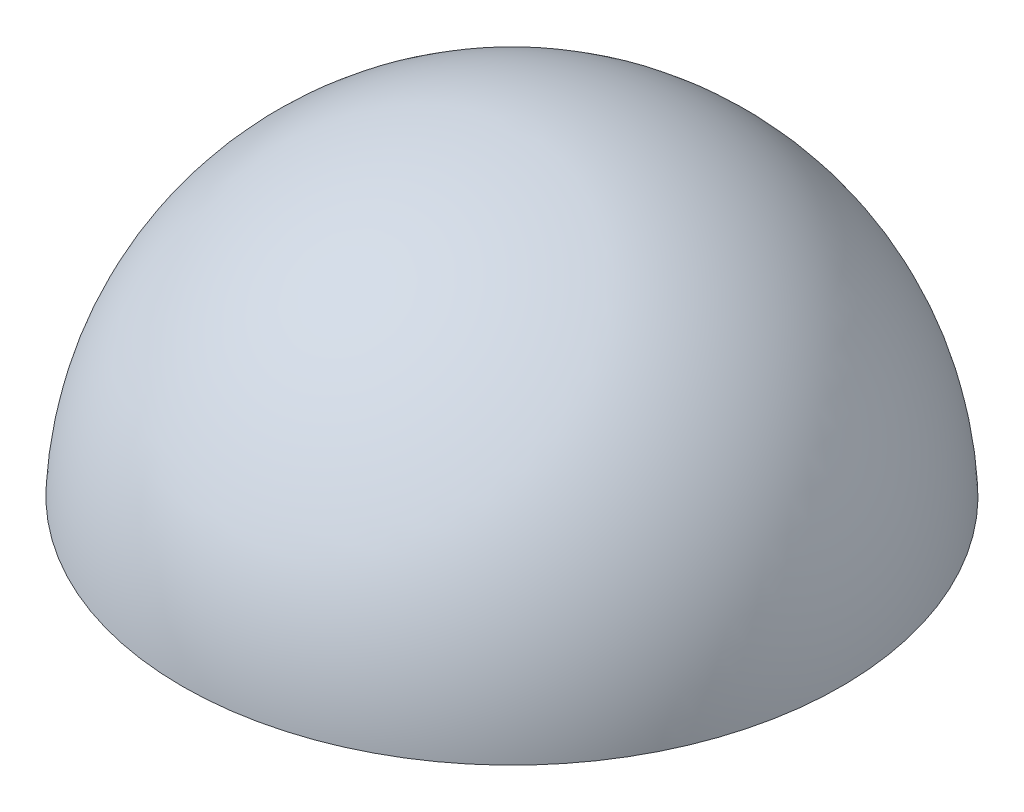
SolidWorks part; units mm, degrees
ref_plane "Front Plane" through (0, 0, 0) normal (0, 0, 1) x (1, 0, 0)
ref_plane "Top Plane" through (0, 0, 0) normal (0, 1, 0) x (1, 0, 0)
ref_plane "Right Plane" through (0, 0, 0) normal (1, 0, 0) x (0, 0, -1)
sketch "Sketch1" plane through (0, 0, 0) normal (0, 1, 0) x (1, 0, 0)
  line L0 (0, -44.45) -> (0, 44.45)
  arc A0 (0, 44.45) -> (0, -44.45) centre (0, 0) ccw
  arc A1 (0, 42.45) -> (0, -42.45) centre (0, 0) ccw
  circle A3 centre (0, 0) radius 44.45 construction
  circle A4 centre (0, 0) radius 42.45 construction
  point P1 (42.45, 0)
  point P6 (42.5077, 12.9959)
  dimension "D1" = 88.9
  dimension "D2" = 2
revolve "Revolve1" add sketch "Sketch1" angle 180 about L0 region at (-43.4561, 0, 0)
sketch "Sketch2" plane through (0, 0, 0) normal (0, 1, 0) x (1, 0, 0)
  circle A0 centre (0, 0) radius 44.45
extrude "Cut-Extrude1" cut sketch "Sketch2" along normal blind 2
sketch "30deg" plane through (0, 0, 0) normal (1, 0, 0) x (0, 0, -1)
  line L0 (0, 0) -> (38.4948, 22.225) construction
  line L1 (0, 0) -> (44.45, 0) construction
  line L7 (0, 0) -> (22.225, 38.4948) construction
  line L8 (0, 0) -> (44.45, 0) construction
  line L10 (0, 0) -> (38.4948, 22.225) construction
  line L25 (0, 0) -> (0, 49000) construction
  dimension "D2" = 3
  dimension "D3" = 30
  dimension "D1" = 44.45
sketch "Sketch4" plane through (0, 0, 0) normal (0, 1, 0) x (1, 0, 0)
  line L0 (0, 0) -> (0, 43.45)
  line L1 (0.5, 44.45) -> (-0.5, 44.45)
  line L2 (-0.5, 43.45) -> (0.5, 43.45)
  line L3 (-0.5, 43.45) -> (-0.5, 44.45)
  line L4 (0.5, 43.45) -> (0.5, 44.45)
  line L5 (0, 0) -> (21.725, 37.6288)
  line L6 (21.292, 37.8788) -> (21.792, 38.7448)
  line L7 (21.292, 37.8788) -> (22.158, 37.3788)
  line L8 (22.158, 37.3788) -> (22.658, 38.2448)
  line L9 (22.658, 38.2448) -> (21.792, 38.7448)
  line L10 (0, 0) -> (37.6288, 21.725)
  line L11 (37.3788, 22.158) -> (38.2448, 22.658)
  line L12 (37.3788, 22.158) -> (37.8788, 21.292)
  line L13 (37.8788, 21.292) -> (38.7448, 21.792)
  line L14 (38.7448, 21.792) -> (38.2448, 22.658)
  line L15 (0, 0) -> (43.45, 0)
  line L16 (43.45, 0.5) -> (44.45, 0.5)
  line L17 (43.45, 0.5) -> (43.45, -0.5)
  line L18 (43.45, -0.5) -> (44.45, -0.5)
  line L19 (44.45, -0.5) -> (44.45, 0.5)
  line L20 (0, 0) -> (37.6288, -21.725)
  line L21 (37.8788, -21.292) -> (38.7448, -21.792)
  line L22 (37.8788, -21.292) -> (37.3788, -22.158)
  line L23 (37.3788, -22.158) -> (38.2448, -22.658)
  line L24 (38.2448, -22.658) -> (38.7448, -21.792)
  line L25 (0, 0) -> (21.725, -37.6288)
  line L26 (22.158, -37.3788) -> (22.658, -38.2448)
  line L27 (22.158, -37.3788) -> (21.292, -37.8788)
  line L28 (21.292, -37.8788) -> (21.792, -38.7448)
  line L29 (21.792, -38.7448) -> (22.658, -38.2448)
  line L30 (0, 0) -> (0, -43.45)
  line L31 (0.5, -43.45) -> (0.5, -44.45)
  line L32 (0.5, -43.45) -> (-0.5, -43.45)
  line L33 (-0.5, -43.45) -> (-0.5, -44.45)
  line L34 (-0.5, -44.45) -> (0.5, -44.45)
  line L35 (0, 0) -> (-21.725, -37.6288)
  line L36 (-21.292, -37.8788) -> (-21.792, -38.7448)
  line L37 (-21.292, -37.8788) -> (-22.158, -37.3788)
  line L38 (-22.158, -37.3788) -> (-22.658, -38.2448)
  line L39 (-22.658, -38.2448) -> (-21.792, -38.7448)
  line L40 (0, 0) -> (-37.6288, -21.725)
  line L41 (-37.3788, -22.158) -> (-38.2448, -22.658)
  line L42 (-37.3788, -22.158) -> (-37.8788, -21.292)
  line L43 (-37.8788, -21.292) -> (-38.7448, -21.792)
  line L44 (-38.7448, -21.792) -> (-38.2448, -22.658)
  line L45 (0, 0) -> (-43.45, 0)
  line L46 (-43.45, -0.5) -> (-44.45, -0.5)
  line L47 (-43.45, -0.5) -> (-43.45, 0.5)
  line L48 (-43.45, 0.5) -> (-44.45, 0.5)
  line L49 (-44.45, 0.5) -> (-44.45, -0.5)
  line L50 (0, 0) -> (-37.6288, 21.725)
  line L51 (-37.8788, 21.292) -> (-38.7448, 21.792)
  line L52 (-37.8788, 21.292) -> (-37.3788, 22.158)
  line L53 (-37.3788, 22.158) -> (-38.2448, 22.658)
  line L54 (-38.2448, 22.658) -> (-38.7448, 21.792)
  line L55 (0, 0) -> (-21.725, 37.6288)
  line L56 (-22.158, 37.3788) -> (-22.658, 38.2448)
  line L57 (-22.158, 37.3788) -> (-21.292, 37.8788)
  line L58 (-21.292, 37.8788) -> (-21.792, 38.7448)
  line L59 (-21.792, 38.7448) -> (-22.658, 38.2448)
  line L60 (0, 0) -> (0, 43.45) construction
  line L61 (0, 0) -> (21.725, 37.6288) construction
  circle A0 centre (0, 0) radius 44.45 construction
  point P7 (0, 44.45)
  point P10 (0, 43.45)
  dimension "D1" = 88.9
  dimension "D2" = 1
  dimension "D3" = 1
  dimension "D5" = 30
  dimension "D4" = 12
ref_plane "Plane1" through (0, 44.45, 0) normal (0, 1, 0) x (1, 0, 0)
sketch "Sketch5" plane through (0, 44.45, 0) normal (0, 1, 0) x (1, 0, 0)
  circle A0 centre (0, 0) radius 0.5
  dimension "D1" = 1
sketch "Sketch6" plane through (0, 0, 0) normal (0, 0, 1) x (1, 0, 0)
  line L0 (44.45, 0) -> (-44.45, 0) construction
  line L1 (-43.45, 0) -> (-44.45, 0) construction
  arc A0 (-44.45, 0) -> (0, 44.45) centre (0, 0) cw
ref_axis "Axis1" through (0, 117.8347, 0) along (0, -1, 0)
sketch "Sketch7" plane through (0, 44.45, 0) normal (0, 1, 0) x (1, 0, 0)
  line L0 (0, 0) -> (0, 88.8986) construction
  line L4 (-0.5, 38.9916) -> (-0.5, 88.8986)
  line L5 (0.5, 38.9916) -> (0.5, 88.8986)
  line L7 (-0.5, 22.7195) -> (-0.5, 37.9915)
  line L9 (0.5, 22.7195) -> (0.5, 37.9915)
  line L10 (0, 0) -> (44.4493, 76.9884) construction
  line L11 (19.0628, 34.0177) -> (44.0163, 77.2384)
  line L12 (19.9288, 33.5177) -> (44.8823, 76.7384)
  line L13 (10.9267, 19.9257) -> (18.5628, 33.1516)
  line L14 (11.7928, 19.4257) -> (19.4288, 32.6516)
  line L17 (0, 0) -> (76.9884, 44.4493) construction
  line L18 (33.5177, 19.9288) -> (76.7384, 44.8823)
  line L19 (34.0177, 19.0628) -> (77.2384, 44.0163)
  line L20 (19.4257, 11.7928) -> (32.6516, 19.4288)
  line L21 (19.9257, 10.9267) -> (33.1516, 18.5628)
  line L24 (0, 0) -> (88.8986, 0) construction
  line L25 (38.9916, 0.5) -> (88.8986, 0.5)
  line L26 (38.9916, -0.5) -> (88.8986, -0.5)
  line L27 (22.7195, 0.5) -> (37.9915, 0.5)
  line L28 (22.7195, -0.5) -> (37.9915, -0.5)
  line L31 (0, 0) -> (76.9884, -44.4493) construction
  line L32 (34.0177, -19.0628) -> (77.2384, -44.0163)
  line L33 (33.5177, -19.9288) -> (76.7384, -44.8823)
  line L34 (19.9257, -10.9267) -> (33.1516, -18.5628)
  line L35 (19.4257, -11.7928) -> (32.6516, -19.4288)
  line L38 (0, 0) -> (44.4493, -76.9884) construction
  line L39 (19.9288, -33.5177) -> (44.8823, -76.7384)
  line L40 (19.0628, -34.0177) -> (44.0163, -77.2384)
  line L41 (11.7928, -19.4257) -> (19.4288, -32.6516)
  line L42 (10.9267, -19.9257) -> (18.5628, -33.1516)
  line L45 (0, 0) -> (0, -88.8986) construction
  line L46 (0.5, -38.9916) -> (0.5, -88.8986)
  line L47 (-0.5, -38.9916) -> (-0.5, -88.8986)
  line L48 (0.5, -22.7195) -> (0.5, -37.9915)
  line L49 (-0.5, -22.7195) -> (-0.5, -37.9915)
  line L52 (0, 0) -> (-44.4493, -76.9884) construction
  line L53 (-19.0628, -34.0177) -> (-44.0163, -77.2384)
  line L54 (-19.9288, -33.5177) -> (-44.8823, -76.7384)
  line L55 (-10.9267, -19.9257) -> (-18.5628, -33.1516)
  line L56 (-11.7928, -19.4257) -> (-19.4288, -32.6516)
  line L59 (0, 0) -> (-76.9884, -44.4493) construction
  line L60 (-33.5177, -19.9288) -> (-76.7384, -44.8823)
  line L61 (-34.0177, -19.0628) -> (-77.2384, -44.0163)
  line L62 (-19.4257, -11.7928) -> (-32.6516, -19.4288)
  line L63 (-19.9257, -10.9267) -> (-33.1516, -18.5628)
  line L66 (0, 0) -> (-88.8986, 0) construction
  line L67 (-38.9916, -0.5) -> (-88.8986, -0.5)
  line L68 (-38.9916, 0.5) -> (-88.8986, 0.5)
  line L69 (-22.7195, -0.5) -> (-37.9915, -0.5)
  line L70 (-22.7195, 0.5) -> (-37.9915, 0.5)
  line L73 (0, 0) -> (-76.9884, 44.4493) construction
  line L74 (-34.0177, 19.0628) -> (-77.2384, 44.0163)
  line L75 (-33.5177, 19.9288) -> (-76.7384, 44.8823)
  line L76 (-19.9257, 10.9267) -> (-33.1516, 18.5628)
  line L77 (-19.4257, 11.7928) -> (-32.6516, 19.4288)
  line L80 (0, 0) -> (-44.4493, 76.9884) construction
  line L81 (-19.9288, 33.5177) -> (-44.8823, 76.7384)
  line L82 (-19.0628, 34.0177) -> (-44.0163, 77.2384)
  line L83 (-11.7928, 19.4257) -> (-19.4288, 32.6516)
  line L84 (-10.9267, 19.9257) -> (-18.5628, 33.1516)
  line L87 (0, 0) -> (0.5, 0) construction
  line L89 (-0.5, 1.866) -> (-0.5, 21.7192)
  line L90 (-0.5, 1.866) -> (-10.4266, 19.0594)
  line L91 (0.5, 1.866) -> (10.4266, 19.0594)
  line L92 (0.5, 1.866) -> (0.5, 21.7192)
  line L93 (1.366, 1.366) -> (18.5594, 11.2926)
  line L94 (1.366, 1.366) -> (11.2926, 18.5594)
  line L95 (1.866, 0.5) -> (21.7192, 0.5)
  line L96 (1.866, 0.5) -> (19.0594, 10.4266)
  line L97 (1.866, -0.5) -> (19.0594, -10.4266)
  line L98 (1.866, -0.5) -> (21.7192, -0.5)
  line L99 (1.366, -1.366) -> (11.2926, -18.5594)
  line L100 (1.366, -1.366) -> (18.5594, -11.2926)
  line L101 (0.5, -1.866) -> (0.5, -21.7192)
  line L102 (0.5, -1.866) -> (10.4266, -19.0594)
  line L103 (-0.5, -1.866) -> (-10.4266, -19.0594)
  line L104 (-0.5, -1.866) -> (-0.5, -21.7192)
  line L105 (-1.366, -1.366) -> (-11.2926, -18.5594)
  line L106 (-1.366, -1.366) -> (-18.5594, -11.2926)
  line L107 (-1.866, -0.5) -> (-21.7192, -0.5)
  line L108 (-1.866, -0.5) -> (-19.0594, -10.4266)
  line L109 (-1.866, 0.5) -> (-19.0594, 10.4266)
  line L110 (-1.866, 0.5) -> (-21.7192, 0.5)
  line L111 (-1.366, 1.366) -> (-11.2926, 18.5594)
  line L112 (-1.366, 1.366) -> (-18.5594, 11.2926)
  circle A0 centre (0, 0) radius 22.225 construction
  circle A1 centre (0, 0) radius 38.4948 construction
  arc A2 (-0.5, 38.9916) -> (-19.0628, 34.0177) centre (0, 0) ccw
  arc A3 (-0.5, 22.7195) -> (-10.9267, 19.9257) centre (0, 0) ccw
  arc A4 (-0.5, 37.9915) -> (-18.5628, 33.1516) centre (0, 0) ccw
  arc A5 (-0.5, 21.7192) -> (-10.4266, 19.0594) centre (0, 0) ccw
  arc A6 (0.5, 88.8986) -> (-0.5, 88.8986) centre (0, 0) ccw
  circle A9 centre (0, 0) radius 88.9 construction
  circle A10 centre (0, 0) radius 38.9948 construction
  circle A11 centre (0, 0) radius 37.9948 construction
  circle A13 centre (0, 0) radius 21.725 construction
  circle A14 centre (0, 0) radius 22.725 construction
  arc A15 (44.8823, 76.7384) -> (44.0163, 77.2384) centre (0, 0) ccw
  arc A16 (77.2384, 44.0163) -> (76.7384, 44.8823) centre (0, 0) ccw
  arc A17 (88.8986, -0.5) -> (88.8986, 0.5) centre (0, 0) ccw
  arc A18 (76.7384, -44.8823) -> (77.2384, -44.0163) centre (0, 0) ccw
  arc A19 (44.0163, -77.2384) -> (44.8823, -76.7384) centre (0, 0) ccw
  arc A20 (-0.5, -88.8986) -> (0.5, -88.8986) centre (0, 0) ccw
  arc A21 (-44.8823, -76.7384) -> (-44.0163, -77.2384) centre (0, 0) ccw
  arc A22 (-77.2384, -44.0163) -> (-76.7384, -44.8823) centre (0, 0) ccw
  arc A23 (-88.8986, 0.5) -> (-88.8986, -0.5) centre (0, 0) ccw
  arc A24 (-76.7384, 44.8823) -> (-77.2384, 44.0163) centre (0, 0) ccw
  arc A25 (-44.0163, 77.2384) -> (-44.8823, 76.7384) centre (0, 0) ccw
  arc A26 (-34.0177, 19.0628) -> (-38.9916, 0.5) centre (0, 0) ccw
  arc A27 (-33.1516, 18.5628) -> (-37.9915, 0.5) centre (0, 0) ccw
  arc A28 (-19.9288, 33.5177) -> (-33.5177, 19.9288) centre (0, 0) ccw
  arc A29 (-19.4288, 32.6516) -> (-32.6516, 19.4288) centre (0, 0) ccw
  arc A30 (19.0628, 34.0177) -> (0.5, 38.9916) centre (0, 0) ccw
  arc A31 (18.5628, 33.1516) -> (0.5, 37.9915) centre (0, 0) ccw
  arc A32 (32.6516, 19.4288) -> (19.4288, 32.6516) centre (0, 0) ccw
  arc A33 (33.5177, 19.9288) -> (19.9288, 33.5177) centre (0, 0) ccw
  arc A34 (37.9915, 0.5) -> (33.1516, 18.5628) centre (0, 0) ccw
  arc A35 (38.9916, 0.5) -> (34.0177, 19.0628) centre (0, 0) ccw
  arc A36 (33.1516, -18.5628) -> (37.9915, -0.5) centre (0, 0) ccw
  arc A37 (34.0177, -19.0628) -> (38.9916, -0.5) centre (0, 0) ccw
  arc A38 (19.4288, -32.6516) -> (32.6516, -19.4288) centre (0, 0) ccw
  arc A39 (19.9288, -33.5177) -> (33.5177, -19.9288) centre (0, 0) ccw
  arc A40 (0.5, -37.9915) -> (18.5628, -33.1516) centre (0, 0) ccw
  arc A41 (0.5, -38.9916) -> (19.0628, -34.0177) centre (0, 0) ccw
  arc A42 (-18.5628, -33.1516) -> (-0.5, -37.9915) centre (0, 0) ccw
  arc A43 (-19.0628, -34.0177) -> (-0.5, -38.9916) centre (0, 0) ccw
  arc A44 (-33.5177, -19.9288) -> (-19.9288, -33.5177) centre (0, 0) ccw
  arc A45 (-32.6516, -19.4288) -> (-19.4288, -32.6516) centre (0, 0) ccw
  arc A46 (-38.9916, -0.5) -> (-34.0177, -19.0628) centre (0, 0) ccw
  arc A47 (-37.9915, -0.5) -> (-33.1516, -18.5628) centre (0, 0) ccw
  arc A48 (-11.7928, 19.4257) -> (-19.4257, 11.7928) centre (0, 0) ccw
  arc A49 (-11.2926, 18.5594) -> (-18.5594, 11.2926) centre (0, 0) ccw
  arc A50 (-19.9257, 10.9267) -> (-22.7195, 0.5) centre (0, 0) ccw
  arc A51 (-19.0594, 10.4266) -> (-21.7192, 0.5) centre (0, 0) ccw
  arc A52 (-21.7192, -0.5) -> (-19.0594, -10.4266) centre (0, 0) ccw
  arc A53 (-22.7195, -0.5) -> (-19.9257, -10.9267) centre (0, 0) ccw
  arc A54 (10.4266, 19.0594) -> (0.5, 21.7192) centre (0, 0) ccw
  arc A55 (10.9267, 19.9257) -> (0.5, 22.7195) centre (0, 0) ccw
  arc A56 (18.5594, 11.2926) -> (11.2926, 18.5594) centre (0, 0) ccw
  arc A57 (19.4257, 11.7928) -> (11.7928, 19.4257) centre (0, 0) ccw
  arc A58 (21.7192, 0.5) -> (19.0594, 10.4266) centre (0, 0) ccw
  arc A59 (22.7195, 0.5) -> (19.9257, 10.9267) centre (0, 0) ccw
  arc A60 (19.9257, -10.9267) -> (22.7195, -0.5) centre (0, 0) ccw
  arc A61 (19.0594, -10.4266) -> (21.7192, -0.5) centre (0, 0) ccw
  arc A62 (11.2926, -18.5594) -> (18.5594, -11.2926) centre (0, 0) ccw
  arc A63 (11.7928, -19.4257) -> (19.4257, -11.7928) centre (0, 0) ccw
  arc A64 (0.5, -22.7195) -> (10.9267, -19.9257) centre (0, 0) ccw
  arc A65 (0.5, -21.7192) -> (10.4266, -19.0594) centre (0, 0) ccw
  arc A66 (-10.4266, -19.0594) -> (-0.5, -21.7192) centre (0, 0) ccw
  arc A67 (-10.9267, -19.9257) -> (-0.5, -22.7195) centre (0, 0) ccw
  arc A68 (-19.4257, -11.7928) -> (-11.7928, -19.4257) centre (0, 0) ccw
  arc A69 (-18.5594, -11.2926) -> (-11.2926, -18.5594) centre (0, 0) ccw
  point P11 (21.725, 0)
  point P13 (22.725, 0)
  point P17 (0.5, 0)
  point P19 (-0.5, 0)
  point P27 (38.9948, 0)
  point P30 (37.9948, 0)
  point P114 (-1.366, 1.366)
  dimension "D5" = 177.8
  dimension "D1" = 0.5
  dimension "D2" = 0.5
  dimension "D6" = 12
sketch "Sketch9" plane through (0, 44.45, 0) normal (0, 1, 0) x (1, 0, 0)
  line L0 (0, 0) -> (0, -88.9)
  circle A0 centre (0, 0) radius 22.225
  circle A1 centre (0, 0) radius 38.4948
  circle A2 centre (0, 0) radius 88.9
  circle A3 centre (0, 0) radius 38.4948 construction
  circle A4 centre (0, 0) radius 22.225 construction
  dimension "D1" = 177.8
sketch "Sketch10" plane through (0, 44.45, 0) normal (0, 1, 0) x (1, 0, 0)
  line L0 (88.9, 0) -> (-88.9, 0) construction
  line L1 (0, 88.9) -> (0, -88.9) construction
  line L2 (-29.64, 88.9) -> (-29.64, -88.9) construction
  line L3 (-59.28, 88.9) -> (-59.28, -88.9) construction
  line L4 (-88.92, 88.9) -> (-88.92, -88.9) construction
  line L5 (29.64, 88.9) -> (29.64, -88.9) construction
  line L6 (59.28, 88.9) -> (59.28, -88.9) construction
  line L7 (88.92, 88.9) -> (88.92, -88.9) construction
  line L8 (-89.42, 88.9) -> (-89.42, -88.9)
  line L9 (-59.78, 88.9) -> (-59.78, 0.5)
  line L10 (-30.14, 88.9) -> (-30.14, 0.5)
  line L11 (-0.5, 88.9) -> (-0.5, 0.5)
  line L12 (29.14, 88.9) -> (29.14, 0.5)
  line L13 (58.78, 88.9) -> (58.78, 0.5)
  line L14 (88.42, 88.9) -> (88.42, 0.5)
  line L15 (-88.42, 88.9) -> (-88.42, 0.5)
  line L16 (-58.78, 88.9) -> (-58.78, 0.5)
  line L17 (-29.14, 88.9) -> (-29.14, 0.5)
  line L18 (0.5, 88.9) -> (0.5, 0.5)
  line L19 (30.14, 88.9) -> (30.14, 0.5)
  line L20 (59.78, 88.9) -> (59.78, 0.5)
  line L21 (89.42, 88.9) -> (89.42, -88.9)
  line L22 (88.42, 0.5) -> (59.78, 0.5)
  line L23 (88.42, -0.5) -> (59.78, -0.5)
  line L24 (-88.42, -0.5) -> (-88.42, -88.9)
  line L25 (88.9, 0.5) -> (-88.9, 0.5) construction
  line L26 (88.9, -0.5) -> (-88.9, -0.5) construction
  line L27 (-59.78, 0.5) -> (-88.42, 0.5)
  line L28 (-88.42, 88.9) -> (-88.42, -88.9) construction
  line L29 (-59.78, -0.5) -> (-88.42, -0.5)
  line L30 (-59.78, -0.5) -> (-59.78, -88.9)
  line L31 (-58.78, -0.5) -> (-58.78, -88.9)
  line L32 (-59.78, 88.9) -> (-59.78, -88.9) construction
  line L33 (-30.14, -0.5) -> (-30.14, -88.9)
  line L34 (-58.78, 88.9) -> (-58.78, -88.9) construction
  line L35 (-30.14, 88.9) -> (-30.14, -88.9) construction
  line L36 (-29.14, -0.5) -> (-29.14, -88.9)
  line L37 (-29.14, 88.9) -> (-29.14, -88.9) construction
  line L38 (-0.5, -0.5) -> (-0.5, -88.9)
  line L39 (-0.5, 88.9) -> (-0.5, -88.9) construction
  line L40 (0.5, -0.5) -> (0.5, -88.9)
  line L41 (0.5, 88.9) -> (0.5, -88.9) construction
  line L42 (29.14, -0.5) -> (29.14, -88.9)
  line L43 (29.14, 88.9) -> (29.14, -88.9) construction
  line L44 (30.14, -0.5) -> (30.14, -88.9)
  line L45 (30.14, 88.9) -> (30.14, -88.9) construction
  line L46 (58.78, -0.5) -> (58.78, -88.9)
  line L47 (58.78, 88.9) -> (58.78, -88.9) construction
  line L48 (59.78, -0.5) -> (59.78, -88.9)
  line L49 (59.78, 88.9) -> (59.78, -88.9) construction
  line L50 (88.42, -0.5) -> (88.42, -88.9)
  line L51 (88.42, 88.9) -> (88.42, -88.9) construction
  line L52 (58.78, 0.5) -> (30.14, 0.5)
  line L53 (58.78, -0.5) -> (30.14, -0.5)
  line L54 (-30.14, 0.5) -> (-58.78, 0.5)
  line L55 (-30.14, -0.5) -> (-58.78, -0.5)
  line L56 (-0.5, 0.5) -> (-29.14, 0.5)
  line L57 (-0.5, -0.5) -> (-29.14, -0.5)
  line L58 (29.14, 0.5) -> (0.5, 0.5)
  line L59 (29.14, -0.5) -> (0.5, -0.5)
  arc A0 (-89.42, 88.9) -> (-88.42, 88.9) centre (-88.92, 88.9) cw
  arc A1 (-89.42, -88.9) -> (-88.42, -88.9) centre (-88.92, -88.9) ccw
  arc A2 (-59.78, 88.9) -> (-58.78, 88.9) centre (-59.28, 88.9) cw
  arc A3 (-59.78, -88.9) -> (-58.78, -88.9) centre (-59.28, -88.9) ccw
  arc A4 (-30.14, 88.9) -> (-29.14, 88.9) centre (-29.64, 88.9) cw
  arc A5 (-30.14, -88.9) -> (-29.14, -88.9) centre (-29.64, -88.9) ccw
  arc A6 (-0.5, 88.9) -> (0.5, 88.9) centre (0, 88.9) cw
  arc A7 (-0.5, -88.9) -> (0.5, -88.9) centre (0, -88.9) ccw
  arc A8 (29.14, 88.9) -> (30.14, 88.9) centre (29.64, 88.9) cw
  arc A9 (29.14, -88.9) -> (30.14, -88.9) centre (29.64, -88.9) ccw
  arc A10 (58.78, 88.9) -> (59.78, 88.9) centre (59.28, 88.9) cw
  arc A11 (58.78, -88.9) -> (59.78, -88.9) centre (59.28, -88.9) ccw
  arc A12 (88.42, 88.9) -> (89.42, 88.9) centre (88.92, 88.9) cw
  arc A13 (88.42, -88.9) -> (89.42, -88.9) centre (88.92, -88.9) ccw
  arc A15 (-88.9, 0.5) -> (-88.92, 0.4996) centre (-88.9, 0) ccw
  arc A16 (-88.92, -0.4996) -> (-88.9, -0.5) centre (-88.9, 0) ccw
  point P4 (0, 0)
  point P8 (0, 0)
  dimension "D1" = 177.8
  dimension "D3" = 0.5
  dimension "D4" = 0.5
  dimension "D5" = 0.5
  dimension "D6" = 0.5
  dimension "D2" = 4
sketch "Sketch13" plane through (0, 44.45, 0) normal (0, 1, 0) x (1, 0, 0)
  line L0 (0, -11.5265) -> (0, 11.5265) construction
  line L1 (-11.5265, 0) -> (11.5265, 0) construction
  line L2 (-11.5265, -0.5) -> (-0.5, -0.5)
  line L3 (-18.1069, 3.2902) -> (-11.5265, 3.2902) construction
  line L4 (-18.1069, 3.2902) -> (-18.1069, -3.2902) construction
  line L5 (-18.1069, -3.2902) -> (-11.5265, -3.2902) construction
  line L6 (-11.5265, 3.2902) -> (-11.5265, -3.2902) construction
  line L7 (-3.2902, 18.1069) -> (3.2902, 18.1069) construction
  line L8 (-3.2902, 18.1069) -> (-3.2902, 11.5265) construction
  line L9 (-3.2902, 11.5265) -> (3.2902, 11.5265) construction
  line L10 (3.2902, 18.1069) -> (3.2902, 11.5265) construction
  line L11 (0.5, -11.5265) -> (0.5, -0.5)
  line L12 (-11.5265, 0.5) -> (-0.5, 0.5)
  line L13 (-0.5, -11.5265) -> (-0.5, -0.5)
  line L14 (-0.5, 0.5) -> (-0.5, 11.5265)
  line L15 (0.5, 0.5) -> (0.5, 11.5265)
  line L16 (-0.5, -11.5265) -> (-0.5, 11.5265) construction
  line L17 (0.5, 0.5) -> (11.5265, 0.5)
  line L18 (0.5, -11.5265) -> (0.5, 11.5265) construction
  line L19 (0.5, -0.5) -> (11.5265, -0.5)
  line L20 (-11.5265, 0.5) -> (11.5265, 0.5) construction
  line L21 (-11.5265, 0.5) -> (-11.5265, -0.5)
  line L22 (-11.5265, -0.5) -> (11.5265, -0.5) construction
  line L23 (11.5265, 0.5) -> (11.5265, -0.5)
  line L24 (-0.5, -11.5265) -> (0.5, -11.5265)
  line L25 (-0.5, 11.5265) -> (0.5, 11.5265)
  line L26 (18.1035, -0.5) -> (29.13, -0.5)
  line L27 (30.13, -11.5265) -> (30.13, -0.5)
  line L28 (18.1035, 0.5) -> (29.13, 0.5)
  line L29 (29.13, -11.5265) -> (29.13, -0.5)
  line L30 (29.13, 0.5) -> (29.13, 11.5265)
  line L31 (30.13, 0.5) -> (30.13, 11.5265)
  line L32 (30.13, 0.5) -> (41.1565, 0.5)
  line L33 (30.13, -0.5) -> (41.1565, -0.5)
  line L34 (18.1035, 0.5) -> (18.1035, -0.5)
  line L35 (41.1565, 0.5) -> (41.1565, -0.5)
  line L36 (29.13, -11.5265) -> (30.13, -11.5265)
  line L37 (29.13, 11.5265) -> (30.13, 11.5265)
  line L38 (29.63, -11.5265) -> (29.63, 11.5265) construction
  line L39 (18.1035, 0) -> (41.1565, 0) construction
  line L40 (11.5231, 3.2902) -> (18.1035, 3.2902) construction
  line L41 (11.5231, 3.2902) -> (11.5231, -3.2902) construction
  line L42 (11.5231, -3.2902) -> (18.1035, -3.2902) construction
  line L43 (18.1035, 3.2902) -> (18.1035, -3.2902) construction
  line L44 (26.3398, 18.1069) -> (32.9202, 18.1069) construction
  line L45 (26.3398, 18.1069) -> (26.3398, 11.5265) construction
  line L46 (26.3398, 11.5265) -> (32.9202, 11.5265) construction
  line L47 (32.9202, 18.1069) -> (32.9202, 11.5265) construction
  line L48 (47.7335, -0.5) -> (58.76, -0.5)
  line L49 (59.76, -11.5265) -> (59.76, -0.5)
  line L50 (47.7335, 0.5) -> (58.76, 0.5)
  line L51 (58.76, -11.5265) -> (58.76, -0.5)
  line L52 (58.76, 0.5) -> (58.76, 11.5265)
  line L53 (59.76, 0.5) -> (59.76, 11.5265)
  line L54 (59.76, 0.5) -> (70.7865, 0.5)
  line L55 (59.76, -0.5) -> (70.7865, -0.5)
  line L56 (47.7335, 0.5) -> (47.7335, -0.5)
  line L57 (70.7865, 0.5) -> (70.7865, -0.5)
  line L58 (58.76, -11.5265) -> (59.76, -11.5265)
  line L59 (58.76, 11.5265) -> (59.76, 11.5265)
  line L60 (59.26, -11.5265) -> (59.26, 11.5265) construction
  line L61 (47.7335, 0) -> (70.7865, 0) construction
  line L62 (41.1531, 3.2902) -> (47.7335, 3.2902) construction
  line L63 (41.1531, 3.2902) -> (41.1531, -3.2902) construction
  line L64 (41.1531, -3.2902) -> (47.7335, -3.2902) construction
  line L65 (47.7335, 3.2902) -> (47.7335, -3.2902) construction
  line L66 (55.9698, 18.1069) -> (62.5502, 18.1069) construction
  line L67 (55.9698, 18.1069) -> (55.9698, 11.5265) construction
  line L68 (55.9698, 11.5265) -> (62.5502, 11.5265) construction
  line L69 (62.5502, 18.1069) -> (62.5502, 11.5265) construction
  line L70 (-11.5265, 29.13) -> (-0.5, 29.13)
  line L71 (0.5, 18.1035) -> (0.5, 29.13)
  line L72 (-11.5265, 30.13) -> (-0.5, 30.13)
  line L73 (-0.5, 18.1035) -> (-0.5, 29.13)
  line L74 (-0.5, 30.13) -> (-0.5, 41.1565)
  line L75 (0.5, 30.13) -> (0.5, 41.1565)
  line L76 (0.5, 30.13) -> (11.5265, 30.13)
  line L77 (0.5, 29.13) -> (11.5265, 29.13)
  line L78 (-11.5265, 30.13) -> (-11.5265, 29.13)
  line L79 (11.5265, 30.13) -> (11.5265, 29.13)
  line L80 (-0.5, 18.1035) -> (0.5, 18.1035)
  line L81 (-0.5, 41.1565) -> (0.5, 41.1565)
  line L82 (18.1035, 29.13) -> (29.13, 29.13)
  line L83 (30.13, 18.1035) -> (30.13, 29.13)
  line L84 (18.1035, 30.13) -> (29.13, 30.13)
  line L85 (29.13, 18.1035) -> (29.13, 29.13)
  line L86 (29.13, 30.13) -> (29.13, 41.1565)
  line L87 (30.13, 30.13) -> (30.13, 41.1565)
  line L88 (30.13, 30.13) -> (41.1565, 30.13)
  line L89 (30.13, 29.13) -> (41.1565, 29.13)
  line L90 (18.1035, 30.13) -> (18.1035, 29.13)
  line L91 (41.1565, 30.13) -> (41.1565, 29.13)
  line L92 (29.13, 18.1035) -> (30.13, 18.1035)
  line L93 (29.13, 41.1565) -> (30.13, 41.1565)
  line L94 (47.7335, 29.13) -> (58.76, 29.13)
  line L95 (59.76, 18.1035) -> (59.76, 29.13)
  line L96 (47.7335, 30.13) -> (58.76, 30.13)
  line L97 (58.76, 18.1035) -> (58.76, 29.13)
  line L98 (58.76, 30.13) -> (58.76, 41.1565)
  line L99 (59.76, 30.13) -> (59.76, 41.1565)
  line L100 (59.76, 30.13) -> (70.7865, 30.13)
  line L101 (59.76, 29.13) -> (70.7865, 29.13)
  line L102 (47.7335, 30.13) -> (47.7335, 29.13)
  line L103 (70.7865, 30.13) -> (70.7865, 29.13)
  line L104 (58.76, 18.1035) -> (59.76, 18.1035)
  line L105 (58.76, 41.1565) -> (59.76, 41.1565)
  line L106 (0, 18.1035) -> (0, 41.1565) construction
  line L107 (-11.5265, 29.63) -> (11.5265, 29.63) construction
  line L108 (-18.1069, 32.9202) -> (-11.5265, 32.9202) construction
  line L109 (-18.1069, 32.9202) -> (-18.1069, 26.3398) construction
  line L110 (-18.1069, 26.3398) -> (-11.5265, 26.3398) construction
  line L111 (-11.5265, 32.9202) -> (-11.5265, 26.3398) construction
  line L112 (-3.2902, 47.7369) -> (3.2902, 47.7369) construction
  line L113 (-3.2902, 47.7369) -> (-3.2902, 41.1565) construction
  line L114 (-3.2902, 41.1565) -> (3.2902, 41.1565) construction
  line L115 (3.2902, 47.7369) -> (3.2902, 41.1565) construction
  line L116 (29.63, 18.1035) -> (29.63, 41.1565) construction
  line L117 (18.1035, 29.63) -> (41.1565, 29.63) construction
  line L118 (11.5231, 32.9202) -> (18.1035, 32.9202) construction
  line L119 (11.5231, 32.9202) -> (11.5231, 26.3398) construction
  line L120 (11.5231, 26.3398) -> (18.1035, 26.3398) construction
  line L121 (18.1035, 32.9202) -> (18.1035, 26.3398) construction
  line L122 (26.3398, 47.7369) -> (32.9202, 47.7369) construction
  line L123 (26.3398, 47.7369) -> (26.3398, 41.1565) construction
  line L124 (26.3398, 41.1565) -> (32.9202, 41.1565) construction
  line L125 (32.9202, 47.7369) -> (32.9202, 41.1565) construction
  line L126 (59.26, 18.1035) -> (59.26, 41.1565) construction
  line L127 (47.7335, 29.63) -> (70.7865, 29.63) construction
  line L128 (41.1531, 32.9202) -> (47.7335, 32.9202) construction
  line L129 (41.1531, 32.9202) -> (41.1531, 26.3398) construction
  line L130 (41.1531, 26.3398) -> (47.7335, 26.3398) construction
  line L131 (47.7335, 32.9202) -> (47.7335, 26.3398) construction
  line L132 (55.9698, 47.7369) -> (62.5502, 47.7369) construction
  line L133 (55.9698, 47.7369) -> (55.9698, 41.1565) construction
  line L134 (55.9698, 41.1565) -> (62.5502, 41.1565) construction
  line L135 (62.5502, 47.7369) -> (62.5502, 41.1565) construction
  line L136 (-11.5265, 58.76) -> (-0.5, 58.76)
  line L137 (0.5, 47.7335) -> (0.5, 58.76)
  line L138 (-11.5265, 59.76) -> (-0.5, 59.76)
  line L139 (-0.5, 47.7335) -> (-0.5, 58.76)
  line L140 (-0.5, 59.76) -> (-0.5, 70.7865)
  line L141 (0.5, 59.76) -> (0.5, 70.7865)
  line L142 (0.5, 59.76) -> (11.5265, 59.76)
  line L143 (0.5, 58.76) -> (11.5265, 58.76)
  line L144 (-11.5265, 59.76) -> (-11.5265, 58.76)
  line L145 (11.5265, 59.76) -> (11.5265, 58.76)
  line L146 (-0.5, 47.7335) -> (0.5, 47.7335)
  line L147 (-0.5, 70.7865) -> (0.5, 70.7865)
  line L148 (18.1035, 58.76) -> (29.13, 58.76)
  line L149 (30.13, 47.7335) -> (30.13, 58.76)
  line L150 (18.1035, 59.76) -> (29.13, 59.76)
  line L151 (29.13, 47.7335) -> (29.13, 58.76)
  line L152 (29.13, 59.76) -> (29.13, 70.7865)
  line L153 (30.13, 59.76) -> (30.13, 70.7865)
  line L154 (30.13, 59.76) -> (41.1565, 59.76)
  line L155 (30.13, 58.76) -> (41.1565, 58.76)
  line L156 (18.1035, 59.76) -> (18.1035, 58.76)
  line L157 (41.1565, 59.76) -> (41.1565, 58.76)
  line L158 (29.13, 47.7335) -> (30.13, 47.7335)
  line L159 (29.13, 70.7865) -> (30.13, 70.7865)
  line L160 (47.7335, 58.76) -> (58.76, 58.76)
  line L161 (59.76, 47.7335) -> (59.76, 58.76)
  line L162 (47.7335, 59.76) -> (58.76, 59.76)
  line L163 (58.76, 47.7335) -> (58.76, 58.76)
  line L164 (58.76, 59.76) -> (58.76, 70.7865)
  line L165 (59.76, 59.76) -> (59.76, 70.7865)
  line L166 (59.76, 59.76) -> (70.7865, 59.76)
  line L167 (59.76, 58.76) -> (70.7865, 58.76)
  line L168 (47.7335, 59.76) -> (47.7335, 58.76)
  line L169 (70.7865, 59.76) -> (70.7865, 58.76)
  line L170 (58.76, 47.7335) -> (59.76, 47.7335)
  line L171 (58.76, 70.7865) -> (59.76, 70.7865)
  line L172 (0, 47.7335) -> (0, 70.7865) construction
  line L173 (-11.5265, 59.26) -> (11.5265, 59.26) construction
  line L174 (-18.1069, 62.5502) -> (-11.5265, 62.5502) construction
  line L175 (-18.1069, 62.5502) -> (-18.1069, 55.9698) construction
  line L176 (-18.1069, 55.9698) -> (-11.5265, 55.9698) construction
  line L177 (-11.5265, 62.5502) -> (-11.5265, 55.9698) construction
  line L178 (-3.2902, 77.3669) -> (3.2902, 77.3669) construction
  line L179 (-3.2902, 77.3669) -> (-3.2902, 70.7865) construction
  line L180 (-3.2902, 70.7865) -> (3.2902, 70.7865) construction
  line L181 (3.2902, 77.3669) -> (3.2902, 70.7865) construction
  line L182 (29.63, 47.7335) -> (29.63, 70.7865) construction
  line L183 (18.1035, 59.26) -> (41.1565, 59.26) construction
  line L184 (11.5231, 62.5502) -> (18.1035, 62.5502) construction
  line L185 (11.5231, 62.5502) -> (11.5231, 55.9698) construction
  line L186 (11.5231, 55.9698) -> (18.1035, 55.9698) construction
  line L187 (18.1035, 62.5502) -> (18.1035, 55.9698) construction
  line L188 (26.3398, 77.3669) -> (32.9202, 77.3669) construction
  line L189 (26.3398, 77.3669) -> (26.3398, 70.7865) construction
  line L190 (26.3398, 70.7865) -> (32.9202, 70.7865) construction
  line L191 (32.9202, 77.3669) -> (32.9202, 70.7865) construction
  line L192 (59.26, 47.7335) -> (59.26, 70.7865) construction
  line L193 (47.7335, 59.26) -> (70.7865, 59.26) construction
  line L194 (41.1531, 62.5502) -> (47.7335, 62.5502) construction
  line L195 (41.1531, 62.5502) -> (41.1531, 55.9698) construction
  line L196 (41.1531, 55.9698) -> (47.7335, 55.9698) construction
  line L197 (47.7335, 62.5502) -> (47.7335, 55.9698) construction
  line L198 (55.9698, 77.3669) -> (62.5502, 77.3669) construction
  line L199 (55.9698, 77.3669) -> (55.9698, 70.7865) construction
  line L200 (55.9698, 70.7865) -> (62.5502, 70.7865) construction
  line L201 (62.5502, 77.3669) -> (62.5502, 70.7865) construction
  circle A0 centre (0, 0) radius 88.9 construction
  point P4 (0, 0)
  point P8 (0, 0)
  point P12 (-11.5265, 0)
  point P35 (29.63, 0)
  point P38 (29.63, 0)
  point P61 (59.26, 0)
  point P64 (59.26, 0)
  point P86 (0, 29.63)
  point P89 (0, 29.63)
  point P112 (29.63, 29.63)
  point P115 (29.63, 29.63)
  point P138 (59.26, 29.63)
  point P141 (59.26, 29.63)
  point P164 (0, 59.26)
  point P167 (0, 59.26)
  point P190 (29.63, 59.26)
  point P193 (29.63, 59.26)
  point P216 (59.26, 59.26)
  point P219 (59.26, 59.26)
  dimension "D1" = 177.8
  dimension "D2" = 29.6333
  dimension "D3" = 0.5
  dimension "D4" = 0.5
  dimension "D5" = 3
  dimension "D6" = 3
sketch "Sketch14" plane through (0, 44.45, 0) normal (0, 1, 0) x (1, 0, 0)
  line L0 (100.7894, -39.8372) -> (100.7894, -62.7386) construction
  line L13 (112.2401, -51.2879) -> (89.3387, -51.2879) construction
  line L14 (112.2401, -50.7879) -> (101.2894, -50.7879)
  line L15 (82.6067, -54.6539) -> (89.3387, -54.6539) construction
  line L16 (82.6067, -54.6539) -> (82.6067, -47.9219) construction
  line L17 (82.6067, -47.9219) -> (89.3387, -47.9219) construction
  line L18 (89.3387, -54.6539) -> (89.3387, -47.9219) construction
  line L19 (82.6067, -54.6539) -> (89.3387, -47.9219) construction
  line L20 (82.6067, -47.9219) -> (89.3387, -54.6539) construction
  line L21 (97.4234, -33.1053) -> (104.1554, -33.1053) construction
  line L22 (97.4234, -33.1053) -> (97.4234, -39.8372) construction
  line L23 (97.4234, -39.8372) -> (104.1554, -39.8372) construction
  line L24 (104.1554, -33.1053) -> (104.1554, -39.8372) construction
  line L25 (97.4234, -33.1053) -> (104.1554, -39.8372) construction
  line L26 (97.4234, -39.8372) -> (104.1554, -33.1053) construction
  line L27 (100.2894, -39.8372) -> (100.2894, -50.7879)
  line L28 (112.2401, -51.7879) -> (101.2894, -51.7879)
  line L29 (101.2894, -39.8372) -> (101.2894, -50.7879)
  line L30 (112.2401, -50.7879) -> (112.2401, -51.7879)
  line L31 (89.3387, -50.7879) -> (89.3387, -51.7879)
  line L32 (100.2894, -39.8372) -> (101.2894, -39.8372)
  line L33 (100.2894, -62.7386) -> (101.2894, -62.7386)
  line L34 (100.2894, -51.7879) -> (100.2894, -62.7386)
  line L35 (100.2894, -51.7879) -> (89.3387, -51.7879)
  line L36 (100.2894, -39.8372) -> (100.2894, -62.7386) construction
  line L37 (101.2894, -51.7879) -> (101.2894, -62.7386)
  line L38 (112.2401, -51.7879) -> (89.3387, -51.7879) construction
  line L39 (100.2894, -50.7879) -> (89.3387, -50.7879)
  line L40 (101.2894, -39.8372) -> (101.2894, -62.7386) construction
  line L42 (112.2401, -50.7879) -> (89.3387, -50.7879) construction
  point P2 (85.9727, -51.2879)
  point P5 (100.7894, -51.2879)
  point P10 (0, 0)
  point P11 (112.0443, -36.79)
  point P13 (100.7894, -36.4712)
  point P29 (91.0957, -29.774)
  point P30 (105.1811, -15.1159)
  point P31 (82.6067, -47.9219)
  dimension "D1" = 0.5
  dimension "D2" = 0.5
  dimension "D3" = 29.6333
